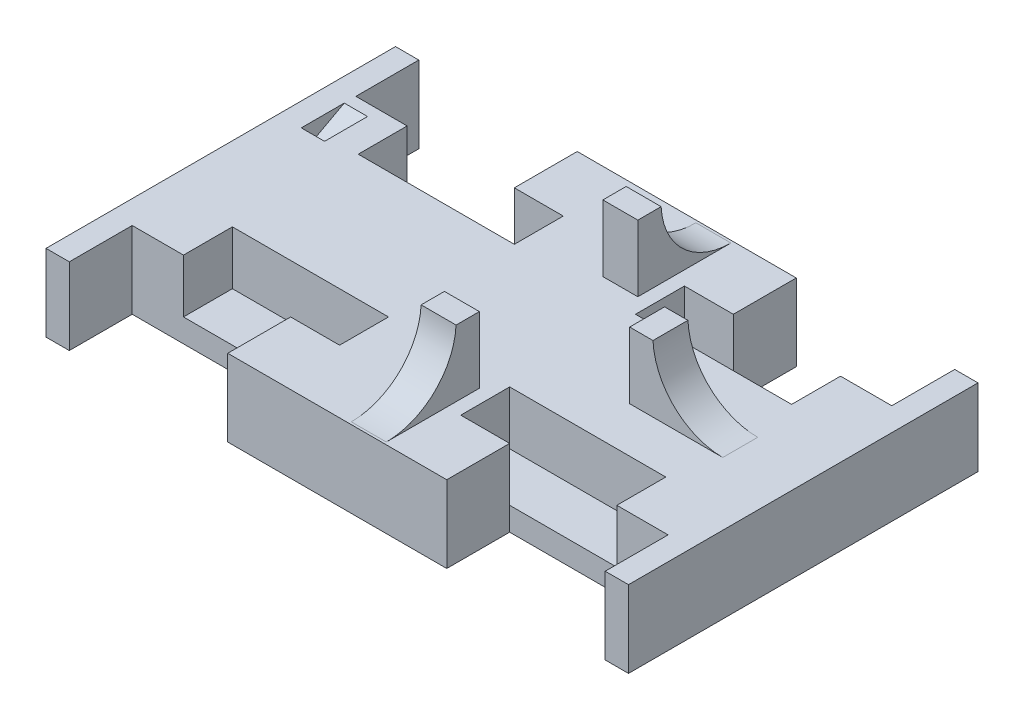
SolidWorks part; units mm, degrees
ref_plane "Front Plane" through (0, 0, 0) normal (0, 0, 1) x (1, 0, 0)
ref_plane "Top Plane" through (0, 0, 0) normal (0, 1, 0) x (1, 0, 0)
ref_plane "Right Plane" through (0, 0, 0) normal (1, 0, 0) x (0, 0, -1)
sketch "Sketch2" plane through (0, 0, 0) normal (0, 1, 0) x (1, 0, 0)
  line L0 (0, 75) -> (0, -75) construction
  line L1 (-125, -75) -> (-115, -75)
  line L2 (-125, -75) -> (-125, 75)
  line L3 (-125, 75) -> (-115, 75)
  line L4 (125, -75) -> (125, 75)
  line L5 (-125, -75) -> (125, 75) construction
  line L6 (-125, 75) -> (125, -75) construction
  line L7 (-125, 0) -> (125, 0) construction
  line L8 (115, 48) -> (47, 48)
  line L10 (-115, 75) -> (-115, 48)
  line L11 (-115, 48) -> (-47, 48)
  line L12 (-47, 75) -> (-47, 48)
  line L17 (47, 75) -> (47, 48)
  line L19 (115, 75) -> (115, 48)
  line L20 (115, -75) -> (115, -48)
  line L22 (47, -75) -> (47, -48)
  line L23 (115, -48) -> (47, -48)
  line L24 (-115, -48) -> (-47, -48)
  line L25 (-47, -75) -> (-47, -48)
  line L27 (-115, -75) -> (-115, -48)
  line L28 (-47, 75) -> (47, 75)
  line L29 (115, 75) -> (125, 75)
  line L30 (115, -75) -> (125, -75)
  line L31 (-47, -75) -> (47, -75)
  line L32 (-125, 75) -> (125, 75) construction
  line L34 (-115, -43) -> (-105, -43)
  line L35 (-115, -43) -> (-115, 43)
  line L36 (-115, 43) -> (-105, 43)
  line L37 (-105, -43) -> (-105, 43)
  line L38 (-115, -43) -> (-105, 43) construction
  line L39 (-115, 43) -> (-105, -43) construction
  point P0 (0, 0)
  point P26 (-110, 0)
  dimension "D1" = 150
  dimension "D2" = 250
  dimension "D3" = 10
  dimension "D4" = 68
  dimension "D5" = 27
  dimension "D6" = 10
  dimension "D7" = 5
extrude "Boss-Extrude1" add sketch "Sketch2" along normal blind 10
sketch "Sketch3" plane through (0, 10, 0) normal (0, 1, 0) x (1, 0, 0)
  line L0 (-115, 43) -> (-105, 43)
  line L1 (-105, 43) -> (-105, -43)
  line L2 (-105, -43) -> (-115, -43)
  line L3 (-115, -43) -> (-115, 43)
  line L4 (-115, 48) -> (-47, 48) construction
  line L5 (-47, 48) -> (-47, 75)
  line L6 (-47, 75) -> (47, 75)
  line L7 (47, 75) -> (47, 48)
  line L8 (93, 48) -> (115, 48)
  line L9 (115, 48) -> (115, 75)
  line L10 (115, 75) -> (125, 75)
  line L11 (125, 75) -> (125, -75)
  line L12 (125, -75) -> (115, -75)
  line L13 (115, -75) -> (115, -48)
  line L14 (115, -48) -> (93, -48)
  line L15 (47, -48) -> (47, -75)
  line L16 (47, -75) -> (-47, -75)
  line L17 (-47, -75) -> (-47, -48)
  line L18 (-93, -48) -> (-115, -48)
  line L19 (-115, -75) -> (-115, -48) construction
  line L20 (-115, -48) -> (-47, -48) construction
  line L21 (-115, -48) -> (-115, -75)
  line L22 (-115, -75) -> (-125, -75)
  line L23 (-125, -75) -> (-125, 75)
  line L24 (-125, 75) -> (-115, 75)
  line L25 (-115, 75) -> (-115, 48)
  line L26 (-81, 48) -> (-81, 75) construction
  line L27 (-93, 48) -> (-93, 27)
  line L28 (-93, 27) -> (-26, 27)
  line L29 (-26, 27) -> (-26, 48)
  line L30 (-26, 48) -> (-47, 48)
  line L31 (-115, 48) -> (-93, 48)
  line L32 (-125, 0) -> (125, 0) construction
  line L33 (0, -75) -> (0, 75) construction
  line L34 (26, 48) -> (47, 48)
  line L35 (26, 27) -> (26, 48)
  line L36 (93, 27) -> (26, 27)
  line L37 (93, 48) -> (93, 27)
  line L38 (93, -48) -> (93, -27)
  line L39 (26, -48) -> (47, -48)
  line L40 (93, -27) -> (26, -27)
  line L41 (26, -27) -> (26, -48)
  line L42 (-26, -27) -> (-26, -48)
  line L43 (-26, -48) -> (-47, -48)
  line L44 (-93, -48) -> (-93, -27)
  line L45 (-93, -27) -> (-26, -27)
  dimension "D1" = 12
  dimension "D2" = 67
  dimension "D3" = 21
extrude "Boss-Extrude2" add sketch "Sketch3" along normal blind 23
sketch "Sketch4" plane through (-105, 0, 0) normal (-1, 0, 0) x (0, 0, 1)
  line L0 (-43, 0) -> (-9.2235, 14.7039)
  line L1 (-9.2235, 14.7039) -> (-43, 33)
  line L2 (0, 33) -> (0, 0) construction
  line L3 (-75, 33) -> (75, 33) construction
  line L4 (43, 0) -> (9.2235, 14.7039)
  line L5 (9.2235, 14.7039) -> (-24.5529, 33)
  line L6 (-43, 0) -> (-43, 33)
  line L7 (43, 0) -> (43, 33)
  line L8 (43, 33) -> (-24.5529, 33)
extrude "Boss-Extrude3" add sketch "Sketch4" along normal up to next
sketch "Sketch5" plane through (-115, 0, 0) normal (1, 0, 0) x (0, 0, -1)
  line L0 (24.5529, 33) -> (43, 33) construction
  circle A0 centre (0, 80.55) radius 47.55
  dimension "D1" = 95.1
extrude "Boss-Extrude4" add sketch "Sketch5" along normal blind 100 and the other way blind 5 separate body
sketch "Sketch7" plane through (0, 33, 0) normal (0, 1, 0) x (1, 0, 0)
  line L0 (-120, 0) -> (-120, 48)
  line L1 (-120, 47.55) -> (-120, -47.55) construction
  line L2 (-120, 48) -> (-93, 48)
  line L3 (-93, 48) -> (-93, 27)
  line L4 (-93, 27) -> (-93, 48) construction
  line L5 (-93, 27) -> (-93, 48) construction
  line L6 (-93, 27) -> (-15, 27)
  line L7 (-15, -47.55) -> (-15, 47.55) construction
  line L8 (-15, 27) -> (-15, -27)
  line L9 (-15, -27) -> (-93, -27)
  line L10 (-93, -27) -> (-93, -48)
  line L11 (-93, -48) -> (-120, -48)
  line L12 (-120, -48) -> (-120, 0)
  line L14 (-105, 43) -> (-115, 43) construction
  line L16 (-105, 43) -> (-115, 43)
  line L17 (-115, 43) -> (-115, 24.5529)
  line L18 (-115, 24.5529) -> (-105, 24.5529)
  line L19 (-105, 24.5529) -> (-105, 43)
extrude "Boss-Extrude6" add sketch "Sketch7" along normal blind 30
sketch "Sketch8" plane through (-105, 0, 0) normal (-1, 0, 0) x (0, 0, 1)
  line L0 (-43, 46.6261) -> (-41.8716, 62.212)
  line L1 (-43, 60.2522) -> (-43, 33) construction
  line L3 (-41.8716, 62.212) -> (26.3558, 62.212) construction
  line L6 (-24.5529, 33) -> (-24.5529, 62.212)
  line L7 (-24.5529, 62.212) -> (-41.8716, 62.212)
  line L8 (-43, 46.6261) -> (-43, 33)
  line L9 (-43, 33) -> (-24.5529, 33)
  line L10 (-43.8716, 62.212) -> (-41.8716, 62.212) construction
  arc A0 (-43, 60.2522) -> (-24.5529, 39.8295) centre (0, 80.55) ccw construction
  point P7 (0, 0)
  point P13 (0, 0)
  point P15 (0, 0)
  point P16 (-43, 62.5696)
  dimension "D1" = 2
extrude "Cut-Extrude2" cut sketch "Sketch8" along normal blind 10 contours L0 L7 L6 L9 L8
sketch "Sketch9" plane through (-105, 0, 0) normal (-1, 0, 0) x (0, 0, 1)
  line L0 (-42.1389, 58.5202) -> (-43, 46.6261)
  line L1 (-43, 60.2522) -> (-43, 33) construction
  line L2 (-43, 46.6261) -> (-43, 62.212)
  line L3 (-43, 62.212) -> (-41.8716, 62.212)
  line L4 (-42.1389, 58.5202) -> (-41.8716, 62.212)
extrude "Boss-Extrude7" add sketch "Sketch9" along normal up to next
sketch "Sketch6" plane through (-15, 0, 0) normal (1, 0, 0) x (0, 0, -1)
  line L0 (0, 128.1) -> (0, 33) construction
  circle A0 centre (0, 80.55) radius 47.55 construction
  circle A1 centre (0, 80.55) radius 45.55
  dimension "D1" = 2
extrude "Cut-Extrude1" cut sketch "Sketch6" against normal blind 100
sketch "Sketch10" plane through (0, 33, 0) normal (0, 1, 0) x (1, 0, 0)
  line L0 (0, 0) -> (125, 0) construction
  line L1 (125, -75) -> (125, 75) construction
  line L2 (5, 34) -> (20, 34)
  line L3 (5, -44) -> (20, -44)
  line L4 (5, -44) -> (5, -34)
  line L5 (5, -34) -> (20, -34)
  line L6 (20, -44) -> (20, -34)
  line L7 (20, 44) -> (20, 34)
  line L8 (5, 44) -> (20, 44)
  line L9 (5, 44) -> (5, 34)
  line L10 (-47, -75) -> (47, -75) construction
  line L11 (-15, -47.55) -> (-15, 47.55) construction
  line L13 (58, -7.5) -> (68, -7.5)
  line L14 (58, -7.5) -> (58, 7.5)
  line L15 (58, 7.5) -> (68, 7.5)
  line L16 (68, -7.5) -> (68, 7.5)
  line L17 (58, -7.5) -> (68, 7.5) construction
  line L18 (58, 7.5) -> (68, -7.5) construction
  point P17 (63, 0)
  dimension "D1" = 41
  dimension "D2" = 10
  dimension "D3" = 15
  dimension "D4" = 20
  dimension "D5" = 67
extrude "Boss-Extrude8" add sketch "Sketch10" along normal blind 28.5
fillet "Fillet1" radius 30 1 edges at (12.5, 33, 44)
fillet "Fillet2" radius 30 1 edges at (12.5, 33, -44)
fillet "Fillet3" radius 30 1 edges at (68, 33, 0)
sketch "Sketch11" plane through (0, 0, 75) normal (0, 0, 1) x (1, 0, 0)
  line L0 (-125, 33) -> (-115, 33) construction
  line L1 (-120, 33) -> (-8.0289, 33)
  line L2 (-120, 33) -> (-120, 132.4253)
  line L3 (-120, 132.4253) -> (-8.0289, 132.4253)
  line L4 (-8.0289, 33) -> (-8.0289, 132.4253)
extrude "Cut-Extrude3" cut sketch "Sketch11" against normal through all
